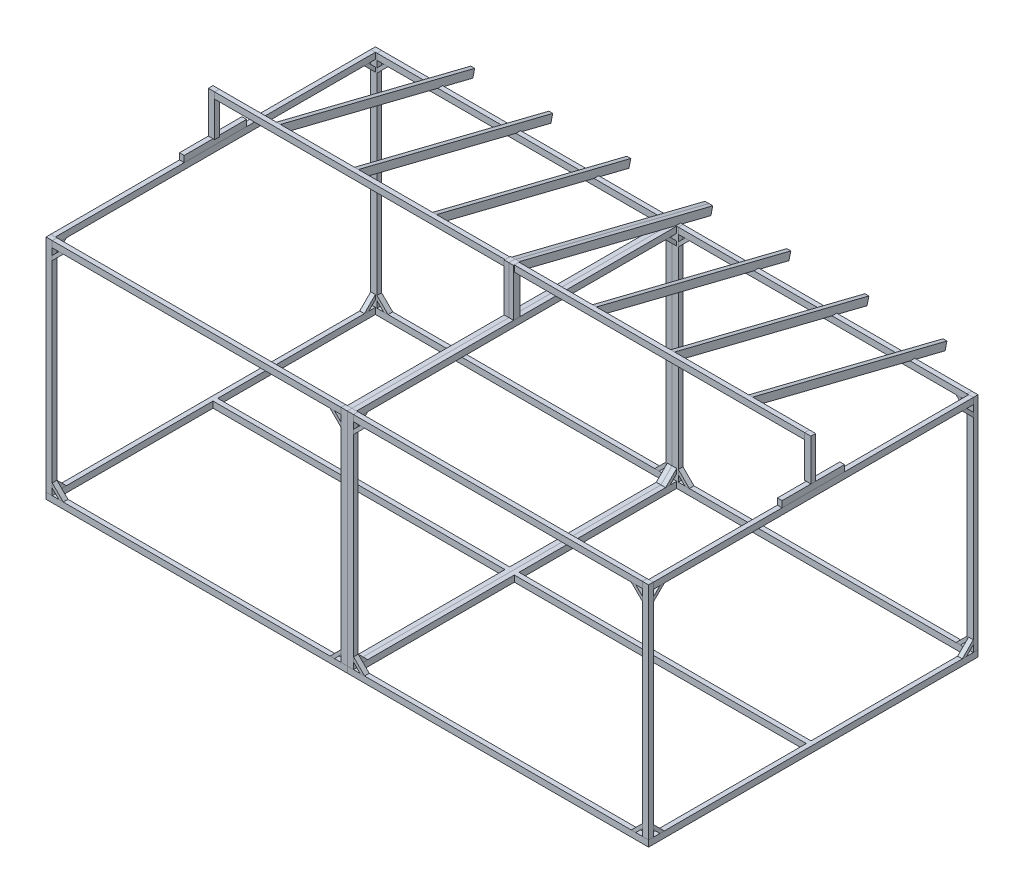
SolidWorks part; units mm, degrees
other "DetailItem8"
other "DetailItem9"
other "DetailItem10"
other "DetailItem11"
other "DetailItem12"
other "DetailItem13"
other "DetailItem14"
other "DetailItem15"
other "DetailItem16"
other "DetailItem17"
ref_plane "Front Plane" through (0, 0, 0) normal (0, 0, 1) x (1, 0, 0)
ref_plane "Top Plane" through (0, 0, 0) normal (0, 1, 0) x (1, 0, 0)
ref_plane "Right Plane" through (0, 0, 0) normal (1, 0, 0) x (0, 0, -1)
other "Configuration Table"
sketch "MetalBase" plane through (0, 0, 0) normal (0, 1, 0) x (1, 0, 0)
  line L0 (-60, -60) -> (7660, -60)
  line L1 (0, 0) -> (7600, 0)
  line L2 (0, 0) -> (0, 2020)
  line L3 (0, 4100) -> (7600, 4100)
  line L4 (7600, 0) -> (7600, 2020)
  line L5 (7660, -60) -> (7660, 4160)
  line L6 (-60, 4160) -> (7660, 4160)
  line L7 (-60, -60) -> (-60, 4160)
  line L8 (0, 2050) -> (7600, 2050) construction
  line L9 (0, 2020) -> (7600, 2020)
  line L10 (0, 2080) -> (7600, 2080)
  line L11 (0, 2080) -> (0, 4100)
  line L12 (7600, 2080) -> (7600, 4100)
  line L13 (0, 0) -> (0, 4100) construction
  line L15 (7600, 0) -> (7600, 4100) construction
  point P15 (7660, 2050)
  dimension "D1" = 4100
  dimension "D2" = 7600
  dimension "D6" = 4220
  dimension "D7" = 7720
  dimension "D3" = 60
  dimension "D4" = 30
  dimension "D5" = 30
sketch "InternalSpace" plane through (0, 0, 0) normal (0, 1, 0) x (1, 0, 0)
  line L26 (50, 50) -> (7550, 50)
  line L27 (7550, 50) -> (7550, 4050)
  line L28 (7550, 4050) -> (50, 4050)
  line L29 (50, 4050) -> (50, 50)
  line L30 (50, 50) -> (7550, 50)
  line L31 (7550, 50) -> (7550, 4050)
  line L32 (7550, 4050) -> (50, 4050)
  line L33 (50, 4050) -> (50, 50)
  dimension "D2" = 4000
  dimension "D3" = 7500
  dimension "D1" = 110
sketch "Furniture" [suppressed] plane through (0, 0, 0) normal (0, 1, 0) x (1, 0, 0)
  line L0 (6750, 2050) -> (6750, 4050)
  line L1 (2200, 2550) -> (1400, 2550)
  line L2 (2200, 2550) -> (2200, 4050)
  line L3 (2200, 4050) -> (1400, 4050)
  line L4 (1400, 2550) -> (1400, 4050)
  line L5 (1050, 50) -> (50, 50)
  line L6 (1050, 50) -> (1050, 2050)
  line L7 (1050, 2050) -> (50, 2050)
  line L8 (50, 50) -> (50, 2050)
  line L9 (6350, 2110) -> (7550, 2110)
  line L10 (2200, 4050) -> (2200, 150)
  line L11 (0, 0) -> (7600, 0) construction
  line L12 (6350, 50) -> (6350, 2110)
  line L13 (6470, 50) -> (6470, 1990)
  line L15 (2200, 2050) -> (7550, 2050) construction
  line L17 (1979.5569, 919.0285) -> (2200, 150)
  line L18 (6350, 150) -> (5722.0427, 459.305)
  line L19 (6710, 1120.0467) -> (7310, 1120.0467)
  line L24 (6710, 1120.0467) -> (6710, 1880.0467)
  line L25 (6710, 1880.0467) -> (7310, 1880.0467)
  line L26 (7310, 1120.0467) -> (7310, 1880.0467)
  line L27 (6350, 2110) -> (5750, 2110)
  line L28 (6350, 2110) -> (6350, 1510)
  line L29 (6350, 1510) -> (5750, 1510)
  line L30 (5750, 2110) -> (5750, 1510)
  line L31 (2320, 2050) -> (4320, 2050) construction
  line L32 (4320, 2050) -> (4320, 4050) construction
  line L33 (2200, 150) -> (2499.3532, 150) construction
  line L34 (2499.3532, 150) -> (2499.3532, 981.1813) construction
  line L35 (2499.3532, 981.1813) -> (2200, 981.1813) construction
  line L36 (2320, 4050) -> (2320, 150)
  line L37 (2200, 150) -> (2200, 50)
  line L38 (50, 50) -> (7550, 50) construction
  line L39 (2320, 150) -> (2320, 50)
  line L40 (7550, 4050) -> (50, 4050) construction
  line L41 (7550, 50) -> (7550, 4050) construction
  line L42 (50, 4050) -> (50, 50) construction
  line L43 (7550, 4050) -> (50, 4050) construction
  line L44 (7550, 50) -> (7550, 4050) construction
  line L45 (50, 50) -> (7550, 50) construction
  line L46 (50, 4050) -> (50, 50) construction
  line L47 (7010, 1120.0467) -> (7010, 1445.9123) construction
  line L48 (6470, 1990) -> (7550, 1990)
  line L49 (-60, -60) -> (-60, 4160) construction
  line L50 (7550, 809.8905) -> (7383.7397, 809.8905)
  line L51 (7550, 809.8905) -> (7550, 230.8186)
  line L52 (7550, 230.8186) -> (7383.7397, 230.8186)
  line L53 (7283.7397, 709.8905) -> (7283.7397, 330.8186)
  line L54 (7660, 4160) -> (-60, 4160) construction
  line L55 (-60, 4160) -> (-60, -60) construction
  line L56 (-60, -60) -> (7660, -60) construction
  line L57 (7660, -60) -> (7660, 4160) construction
  arc A1 (1979.5569, 919.0285) -> (1414.1883, 0) centre (2200, 150) ccw construction
  arc A2 (5722.0427, 459.305) -> (6350, 850) centre (6350, 150) cw construction
  arc A3 (7383.7397, 230.8186) -> (7283.7397, 330.8186) centre (7383.7397, 330.8186) cw
  arc A4 (7383.7397, 809.8905) -> (7283.7397, 709.8905) centre (7383.7397, 709.8905) ccw
  point P56 (7010, 1990)
  dimension "D13" = 600
  dimension "D21" = 100
  dimension "D1" = 1500
  dimension "D2" = 800
  dimension "D3" = 2000
  dimension "D4" = 1000
  dimension "D5" = 100
  dimension "D6" = 60
  dimension "D7" = 700
  dimension "D8" = 600
  dimension "D9" = 2260
  dimension "D10" = 800
  dimension "D11" = 100
  dimension "D12" = 760
  dimension "D14" = 2000
  dimension "D15" = 800
  dimension "D16" = 2000
  dimension "D17" = 600
  dimension "D18" = 60
  dimension "D19" = 4150
  dimension "D20" = 120
  dimension "D22" = 120
  dimension "D23" = 110
  dimension "D25" = 4220
  dimension "D26" = 1200
  dimension "D27" = 4030
  dimension "D24" = 110
sketch "Metal frame" plane through (0, 0, 0) normal (0, 1, 0) x (1, 0, 0)
  line L0 (0, 4100) -> (7600, 4100) construction
  line L1 (0, 4100) -> (7600, 4100)
  line L3 (0, 0) -> (0, 2020)
  line L4 (0, 0) -> (7600, 0) construction
  line L5 (0, 0) -> (7600, 0)
  line L7 (7600, 0) -> (7600, 2020)
  line L8 (-60, 4160) -> (7660, 4160)
  line L9 (7660, -60) -> (7660, 4160)
  line L10 (-60, -60) -> (7660, -60)
  line L11 (-60, -60) -> (-60, 4160)
  line L12 (0, 2050) -> (62.1159, 2050) construction
  line L13 (7600, 2080) -> (0, 2080)
  line L15 (7600, 2020) -> (0, 2020)
  line L17 (7600, 2080) -> (7600, 4100)
  line L18 (0, 2080) -> (0, 4100)
  line L19 (7600, 0) -> (7600, 4100) construction
  line L21 (0, 0) -> (0, 4100) construction
  point P14 (-60, 2050)
  dimension "D2" = 7720
  dimension "D3" = 4220
  dimension "D4" = 60
  dimension "D1" = 60
sketch "Walls bottom" plane through (0, 0, 0) normal (0, 1, 0) x (1, 0, 0)
  line L0 (-60, 4160) -> (7660, 4160) construction
  line L2 (-60, -60) -> (7660, -60) construction
  line L3 (7660, -60) -> (7660, 4160) construction
  line L4 (-60, -60) -> (-60, 4160) construction
  line L5 (-60, -60) -> (7660, -60)
  line L6 (7660, -60) -> (7660, 4160)
  line L7 (-60, 4160) -> (7660, 4160)
  line L8 (-60, -60) -> (-60, 4160)
  line L9 (40, 40) -> (40, 4060)
  line L10 (40, 4060) -> (7560, 4060)
  line L11 (7560, 40) -> (7560, 4060)
  line L12 (40, 40) -> (7560, 40)
  dimension "D2" = 4020
  dimension "D3" = 7520
  dimension "D4" = 7720
  dimension "D5" = 4220
  dimension "D1" = 100
sketch "Sketch15" [suppressed] plane through (0, 0, 0) normal (0, 1, 0) x (1, 0, 0)
  line L2 (7550, 50) -> (5502.4266, 50)
  line L3 (7550, 50) -> (7550, 1250)
  line L4 (7550, 1250) -> (5502.4266, 1250)
  line L5 (5502.4266, 50) -> (5502.4266, 1250)
  dimension "D1" = 1200
extrude "MetalFrame" add sketch "Metal frame" against normal blind 80 contours L11 L10 L9 L8 L15 L7 L5 L3 L13 L18 L1 L17 region at (3800, 0, -2050)
sketch "Sketch18" plane through (0, 0, 0) normal (0, 1, 0) x (1, 0, 0)
  line L0 (0, 0) -> (7600, 0) construction
  line L1 (3800, -1014.8769) -> (8467.9433, -1014.8769)
  line L2 (3800, -1014.8769) -> (3800, 5493.3133)
  line L3 (3800, 5493.3133) -> (8467.9433, 5493.3133)
  line L4 (8467.9433, -1014.8769) -> (8467.9433, 5493.3133)
  point P6 (3800, 0)
extrude "Cut-Extrude1" cut sketch "Sketch18" against normal through all
sketch "Sketch19" plane through (0, 0, 0) normal (0, 1, 0) x (1, 0, 0)
  line L0 (0, 0) -> (3800, 0) construction
  line L1 (3800, 4100) -> (3740, 4100)
  line L2 (3800, 4100) -> (3800, 0)
  line L3 (3800, 0) -> (3740, 0)
  line L4 (3740, 4100) -> (3740, 0)
  dimension "D1" = 60
extrude "Boss-Extrude1" add sketch "Sketch19" against normal blind 80
sketch "Roof" plane through (0, 0, 0) normal (1, 0, 0) x (0, 0, -1)
  line L0 (2050, 0) -> (2050, 3357.5) construction
  line L1 (4160, 0) -> (-60, 0) construction
  line L2 (4160, 0) -> (4160, 2830) construction
  line L3 (4160, 2830) -> (2050, 3357.5) construction
  line L4 (2050, 3357.5) -> (5424.8088, 3357.5) construction
  line L5 (4160, 2830) -> (4548.057, 2732.9857) construction
  line L6 (4160, 150) -> (-211.81, 150) construction
  line L7 (4160, 2830) -> (2960, 2830)
  line L8 (2960, 2830) -> (2960, 3130)
  line L9 (4160, 2750) -> (2401.0379, 2750) construction
  dimension "D2" = 1200
  dimension "D3" = 150
  dimension "D4" = 2174.9382
  dimension "D5" = 400
  dimension "D6" = 2574.9382
  dimension "D7" = 2830
  dimension "D8" = 300
  dimension "D9" = 3207.5
  dimension "D10" = 14.036
  dimension "D11" = 80
  dimension "D12" = 2600
sketch "Sketch23" plane through (-60, 0, 0) normal (1, 0, 0) x (0, 0, -1)
  line L0 (2050, 0) -> (2050, 3357.5) construction
  line L1 (4160, 0) -> (4100, 0)
  line L2 (4160, 0) -> (4160, 2830)
  line L3 (4160, 2830) -> (4100, 2830)
  line L4 (4100, 0) -> (4100, 2830)
  line L5 (0, 0) -> (0, 2830)
  line L6 (-60, 2830) -> (0, 2830)
  line L7 (-60, 0) -> (-60, 2830)
  line L8 (-60, 0) -> (0, 0)
  line L10 (0, 2830) -> (4100, 2830)
  line L11 (0, 2830) -> (0, 2750)
  line L12 (0, 2750) -> (4100, 2750)
  line L13 (4100, 2830) -> (4100, 2750)
  line M8 (-60, 0) -> (4160, 0)
  dimension "D1" = 60
  dimension "D2" = 80
extrude "Boss-Extrude5" add sketch "Sketch23" along normal blind 80 separate body contours L4 L3 L2 M8 | L7 L6 L5 M8 region at (-60, 1415, -4130) region at (-60, 1415, 30)
extrude "Boss-Extrude6" add sketch "Sketch23<3>" along normal blind 60 separate body contours L0 L12 L5 L10 | L12 L0 L10 L4 region at (-60, 2790, -1025) region at (-60, 2790, -3075)
sketch "Sketch23<3>" plane through (-60, 0, 0) normal (1, 0, 0) x (0, 0, -1) same geometry as "Sketch23"
extrude "Boss-Extrude7" add sketch "Sketch23<5>" against normal blind 80 from surface separate body contours L4 L3 L2 M8 | L7 L6 L5 M8 region at (-60, 1415, -4130) region at (-60, 1415, 30) starting at face at (3800, -40, -2050)
sketch "Sketch23<5>" plane through (-60, 0, 0) normal (1, 0, 0) x (0, 0, -1) same geometry as "Sketch23"
extrude "Boss-Extrude8" add sketch "Sketch23<6>" against normal blind 60 from surface separate body contours L12 L0 L10 L4 | L0 L12 L5 L10 region at (-60, 2790, -1025) region at (-60, 2790, -3075) starting at face at (3800, 1415, 30)
sketch "Sketch23<6>" plane through (-60, 0, 0) normal (1, 0, 0) x (0, 0, -1) same geometry as "Sketch23"
sketch "Sketch24" plane through (0, 2830, 0) normal (0, 1, 0) x (1, 0, 0)
  line L1 (20, 4160) -> (3720, 4160)
  line L2 (20, 4160) -> (20, 4100)
  line L3 (20, 4100) -> (3720, 4100)
  line L4 (3720, 4160) -> (3720, 4100)
  line L5 (20, 0) -> (3720, 0)
  line L6 (20, 0) -> (20, -60)
  line L7 (20, -60) -> (3720, -60)
  line L8 (3720, 0) -> (3720, -60)
extrude "Boss-Extrude9" add sketch "Sketch24" against normal blind 80 separate body
sketch "Sketch25" plane through (3800, 0, 0) normal (1, 0, 0) x (0, 0, -1)
  line L5 (2020, 2910) -> (2080, 2910)
  line L6 (2020, 2910) -> (2020, 3440)
  line L7 (2020, 3440) -> (2080, 3440)
  line L8 (2080, 2910) -> (2080, 3440)
  line L9 (2050, 0) -> (2050, 3357.5) construction
  line L10 (0, 2830) -> (4100, 2830) construction
  line L12 (1650, 2830) -> (2450, 2830)
  line L13 (1650, 2830) -> (1650, 2910)
  line L14 (1650, 2910) -> (2450, 2910)
  line L15 (2450, 2830) -> (2450, 2910)
  point P7 (2050, 3440)
  point P11 (2050, 2910)
  line M8 (4100, 2830) -> (0, 2830)
  dimension "D1" = 530
  dimension "D2" = 60
  dimension "D4" = 800
  dimension "D5" = 80
extrude "Boss-Extrude10" add sketch "Sketch25" along normal blind 80 from surface separate body contours L5 L8 L7 L6 region at (3800, 3175, -2050) starting at face at (-60, 2790, -2050)
extrude "Boss-Extrude13" add sketch "Sketch25<4>" against normal blind 60 from surface separate body contours L15 L14 L5 L13 M8 region at (3800, 2870, -2050) starting at face at (0, 2790, -2050)
sketch "Sketch25<4>" plane through (3800, 0, 0) normal (1, 0, 0) x (0, 0, -1) same geometry as "Sketch25"
extrude "Boss-Extrude20" add sketch "Sketch25<5>" against normal blind 60 separate body contours L15 L14 L5 L13 M8 region at (3800, 2870, -2050)
sketch "Sketch25<5>" plane through (3800, 0, 0) normal (1, 0, 0) x (0, 0, -1) same geometry as "Sketch25"
sketch "Sketch33" plane through (0, 2910, 0) normal (0, 1, 0) x (1, 0, 0)
  line L0 (3740, 1650) -> (3740, 2450) construction
  line L1 (3740, 2090) -> (3800, 2090)
  line L2 (3740, 2090) -> (3740, 2010)
  line L3 (3740, 2010) -> (3800, 2010)
  line L4 (3800, 2090) -> (3800, 2010)
  line L5 (3800, 1650) -> (3800, 2450) construction
  point P8 (3740, 2050)
  point P9 (3740, 2050)
  dimension "D1" = 80
extrude "Boss-Extrude21" add sketch "Sketch33" along normal up to surface (530 mm away) separate body up to face at (-20, 3440, -2050)
sketch "Sketch26" plane through (3800, 0, 0) normal (1, 0, 0) x (0, 0, -1)
  line L0 (4548.057, 2717.9857) -> (4160, 2815)
  line L1 (4548.057, 2717.9857) -> (4572.3106, 2815)
  line L3 (4572.3106, 2815) -> (2080, 3438.0776)
  line L4 (4100, 2815) -> (4100, 2830) construction
  line L5 (4100, 2830) -> (4160, 2830)
  line L6 (4160, 2830) -> (4160, 2815)
  line L7 (2080, 3335) -> (2080, 3438.0776)
  line L8 (4100, 2830) -> (2080, 3335)
  dimension "D1" = 100
extrude "Boss-Extrude12" add sketch "Sketch26" against normal blind 50 separate body
pattern_linear "LPattern1" count 4 spacing 1000 along (-1, 0, 0) of bodies 346
ref_plane "Plane1" through (1870, 0, 0) normal (-1, 0, 0) x (0, 0, 1)
sketch "Sketch27" plane through (3740, 0, 0) normal (-1, 0, 0) x (0, 0, 1)
  line L0 (-2020, 2910) -> (-2020, 3440) construction
  line L1 (-2080, 3440) -> (-2020, 3440)
  line L2 (-2080, 3440) -> (-2080, 3360)
  line L3 (-2080, 3360) -> (-2020, 3360)
  line L4 (-2020, 3440) -> (-2020, 3360)
  line L5 (-2050, 0) -> (-2050, 3357.5) construction
  point P4 (-2050, 3440)
  dimension "D1" = 80
  dimension "D2" = 60
extrude "Boss-Extrude22" add sketch "Sketch27" along normal up to surface (3720 mm away) separate body up to face at (20, 3175, -2050)
mirror "Mirror2" about plane through (3800, -80, 1014.8769) normal (-1, 0, 0) of bodies 336 338 340 342 335 337 339 341 330 412 411 349 348 347 346 410 350 351 354 352 353
sketch "Sketch28" plane through (0, 0, 60) normal (0, 0, 1) x (1, 0, 0)
  line L0 (20, 2665.1472) -> (104.8528, 2750)
  line L1 (20, 2750) -> (3720, 2750) construction
  line L2 (20, 0) -> (20, 2830) construction
  line L3 (20, 2608.5786) -> (161.4214, 2750)
  line L4 (20, 2665.1472) -> (20, 2750) construction
  line L5 (20, 2750) -> (104.8528, 2750) construction
  line L6 (3720, 2750) -> (20, 0) construction
  line L7 (20, 2750) -> (3720, 0) construction
  line L8 (104.8528, 2750) -> (161.4214, 2750)
  line L9 (20, 2665.1472) -> (20, 2608.5786)
  line L10 (1870, 1375) -> (1870, 2476.0047) construction
  line L11 (1870, 1375) -> (689.8346, 1375) construction
  line L12 (20, 0) -> (104.8528, 0) construction
  line L13 (20, 84.8528) -> (20, 0) construction
  line L14 (20, 84.8528) -> (20, 141.4214)
  line L15 (104.8528, 0) -> (161.4214, 0)
  line L16 (20, 141.4214) -> (161.4214, 0)
  line L17 (20, 84.8528) -> (104.8528, 0)
  line L18 (3720, 84.8528) -> (3720, 0) construction
  line L19 (3720, 0) -> (3635.1472, 0) construction
  line L20 (3720, 2750) -> (3635.1472, 2750) construction
  line L21 (3720, 2665.1472) -> (3720, 2750) construction
  line L22 (3720, 84.8528) -> (3635.1472, 0)
  line L23 (3720, 141.4214) -> (3578.5786, 0)
  line L24 (3635.1472, 0) -> (3578.5786, 0)
  line L25 (3720, 84.8528) -> (3720, 141.4214)
  line L26 (3720, 2665.1472) -> (3720, 2608.5786)
  line L27 (3635.1472, 2750) -> (3578.5786, 2750)
  line L28 (3720, 2608.5786) -> (3578.5786, 2750)
  line L29 (3720, 2665.1472) -> (3635.1472, 2750)
  line L30 (3800, -80) -> (3800, -237.922) construction
  line L31 (3880, 2665.1472) -> (3880, 2750) construction
  line L32 (3880, 2750) -> (3964.8528, 2750) construction
  line L33 (3880, 0) -> (3964.8528, 0) construction
  line L34 (3880, 84.8528) -> (3880, 0) construction
  line L35 (7580, 84.8528) -> (7580, 0) construction
  line L36 (7580, 0) -> (7495.1472, 0) construction
  line L37 (5730, 1375) -> (6910.1654, 1375) construction
  line L38 (5730, 1375) -> (5730, 2476.0047) construction
  line L39 (7580, 2750) -> (3880, 0) construction
  line L40 (3880, 2750) -> (7580, 0) construction
  line L41 (7580, 2750) -> (7495.1472, 2750) construction
  line L42 (7580, 2665.1472) -> (7580, 2750) construction
  line L43 (3880, 2665.1472) -> (3964.8528, 2750)
  line L44 (3880, 2608.5786) -> (4021.4214, 2750)
  line L45 (3964.8528, 2750) -> (4021.4214, 2750)
  line L46 (3880, 2665.1472) -> (3880, 2608.5786)
  line L47 (3880, 84.8528) -> (3880, 141.4214)
  line L48 (3964.8528, 0) -> (4021.4214, 0)
  line L49 (3880, 141.4214) -> (4021.4214, 0)
  line L50 (3880, 84.8528) -> (3964.8528, 0)
  line L51 (7580, 84.8528) -> (7495.1472, 0)
  line L52 (7580, 141.4214) -> (7438.5786, 0)
  line L53 (7495.1472, 0) -> (7438.5786, 0)
  line L54 (7580, 84.8528) -> (7580, 141.4214)
  line L55 (7580, 2665.1472) -> (7580, 2608.5786)
  line L56 (7495.1472, 2750) -> (7438.5786, 2750)
  line L57 (7580, 2608.5786) -> (7438.5786, 2750)
  line L58 (7580, 2665.1472) -> (7495.1472, 2750)
  point P14 (1870, 1375)
  point P58 (5730, 1375)
  dimension "D1" = 40
  dimension "D2" = 200
extrude "Boss-Extrude15" add sketch "Sketch28" against normal blind 60 separate body
ref_plane "Plane2" through (0, 0, -2050) normal (0, 0, 1) x (1, 0, 0)
mirror "Mirror5" about plane through (0, 0, -2050) normal (0, 0, 1) of bodies 379 382 378 377 380 381 384 383
sketch "Sketch29" plane through (-60, 0, 0) normal (-1, 0, 0) x (0, 0, 1)
  line L0 (-141.4214, 2750) -> (0, 2608.5786)
  line L1 (0, 2750) -> (-4100, 2750) construction
  line L2 (0, 0) -> (0, 2830) construction
  line L3 (0, 2608.5786) -> (0, 2665.1472)
  line L4 (0, 2665.1472) -> (-84.8528, 2750)
  line L5 (-84.8528, 2750) -> (-141.4214, 2750)
  line L6 (-141.4214, 2750) -> (0, 2750) construction
  line L7 (0, 2750) -> (0, 2608.5786) construction
  line L8 (-4100, 2750) -> (0, 0) construction
  line L9 (0, 2750) -> (-4100, 0) construction
  line L10 (-2050, 1375) -> (-2050, 2472.0101) construction
  line L11 (-2050, 0) -> (-2050, 3357.5) construction
  line L12 (-2050, 1375) -> (-3378.9698, 1375) construction
  line L13 (-4100, 2750) -> (-4100, 2608.5786) construction
  line L14 (-3958.5786, 2750) -> (-4100, 2750) construction
  line L15 (-4015.1472, 2750) -> (-3958.5786, 2750)
  line L16 (-4100, 2665.1472) -> (-4015.1472, 2750)
  line L17 (-4100, 2608.5786) -> (-4100, 2665.1472)
  line L18 (-3958.5786, 2750) -> (-4100, 2608.5786)
  line L19 (-3958.5786, 0) -> (-4100, 0) construction
  line L20 (-4100, 0) -> (-4100, 141.4214) construction
  line L21 (0, 0) -> (0, 141.4214) construction
  line L22 (-141.4214, 0) -> (0, 0) construction
  line L23 (-3958.5786, 0) -> (-4100, 141.4214)
  line L24 (-4100, 141.4214) -> (-4100, 84.8528)
  line L25 (-4100, 84.8528) -> (-4015.1472, 0)
  line L26 (-4015.1472, 0) -> (-3958.5786, 0)
  line L27 (-84.8528, 0) -> (-141.4214, 0)
  line L28 (0, 84.8528) -> (-84.8528, 0)
  line L29 (0, 141.4214) -> (0, 84.8528)
  line L30 (-141.4214, 0) -> (0, 141.4214)
  dimension "D1" = 200
  dimension "D2" = 40
extrude "Boss-Extrude16" add sketch "Sketch29" against normal blind 60 separate body
extrude "Boss-Extrude17" add sketch "Sketch29<2>" against normal blind 60 from surface separate body starting at face at (3740, 2790, -2050)
sketch "Sketch29<2>" plane through (-60, 0, 0) normal (-1, 0, 0) x (0, 0, 1) same geometry as "Sketch29"
extrude "Boss-Extrude18" add sketch "Sketch29<4>" against normal blind 60 from surface separate body starting at face at (3800, 2790, -2050)
sketch "Sketch29<4>" plane through (-60, 0, 0) normal (-1, 0, 0) x (0, 0, 1) same geometry as "Sketch29"
extrude "Boss-Extrude19" add sketch "Sketch29<5>" against normal blind 60 from surface separate body starting at face at (7600, 2790, -2050)
sketch "Sketch29<5>" plane through (-60, 0, 0) normal (-1, 0, 0) x (0, 0, 1) same geometry as "Sketch29"
delete or keep bodies "Body-Delete/Keep 1" type delete bodies bodies 410 415
sketch "Sketch34" plane through (0, 2910, 0) normal (0, -1, 0) x (1, 0, 0)
  line L4 (3740, -2010) -> (3740, -2090)
  line L5 (3740, -2090) -> (3800, -2090)
  line L6 (3800, -2090) -> (3800, -2010)
  line L7 (3800, -2010) -> (3740, -2010)
  line L8 (3740, -2010) -> (3740, -2090)
  line L9 (3740, -2090) -> (3800, -2090)
  line L10 (3800, -2090) -> (3800, -2010)
  line L11 (3800, -2010) -> (3740, -2010)
  dimension "D1" = 0
extrude "Boss-Extrude23" add sketch "Sketch34" along normal up to surface (80 mm away) up to face at (3830, 2830, -2050)
sketch "Sketch35" plane through (0, 2910, 0) normal (0, -1, 0) x (1, 0, 0)
  line L4 (3860, -2090) -> (3860, -2010)
  line L5 (3860, -2010) -> (3800, -2010)
  line L6 (3800, -2010) -> (3800, -2090)
  line L7 (3800, -2090) -> (3860, -2090)
  line L8 (3860, -2090) -> (3860, -2010)
  line L9 (3860, -2010) -> (3800, -2010)
  line L10 (3800, -2010) -> (3800, -2090)
  line L11 (3800, -2090) -> (3860, -2090)
  dimension "D1" = 0
extrude "Boss-Extrude24" add sketch "Sketch35" along direction (0, -1, 0) on the side of the normal up to surface (80 mm away) up to face at (3830, 2830, -2050)
